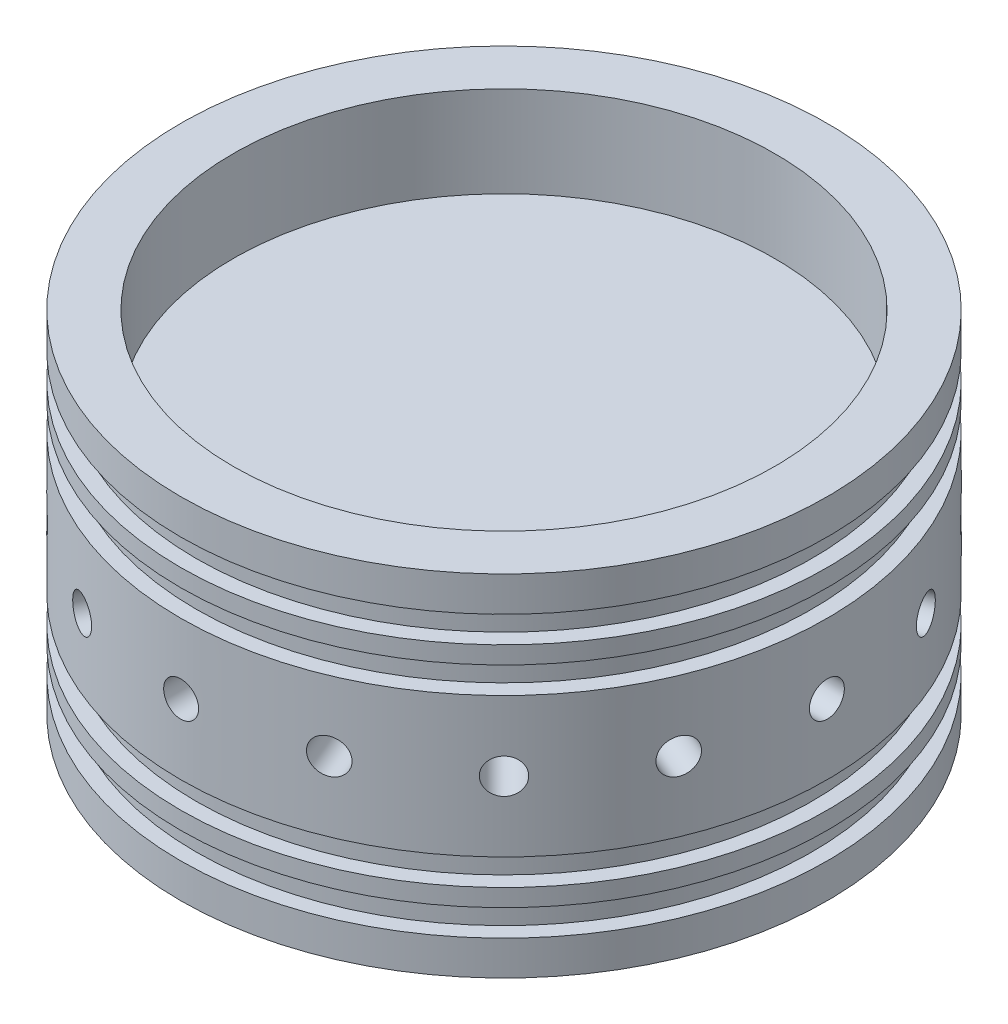
SolidWorks part; units mm, degrees
material "6061-T6 (SS)"
ref_plane "Front Plane" through (0, 0, 0) normal (0, 0, 1) x (1, 0, 0)
ref_plane "Top Plane" through (0, 0, 0) normal (0, 1, 0) x (1, 0, 0)
ref_plane "Right Plane" through (0, 0, 0) normal (1, 0, 0) x (0, 0, -1)
sketch "Sketch1" plane through (0, 0, 0) normal (0, 0, 1) x (1, 0, 0)
  line L11 (0, 0) -> (-58.7375, 0)
  line L13 (-58.7375, 31.8262) -> (-49.2125, 31.8262)
  line L14 (0, 0) -> (0, 15.3162)
  line L15 (0, 15.3162) -> (-49.2125, 15.3162)
  line L16 (-49.2125, 15.3162) -> (-49.2125, 31.8262)
  line L17 (0, 0) -> (0, -15.24)
  line L19 (-58.7375, -31.75) -> (-49.2125, -31.75)
  line L20 (-49.2125, -31.75) -> (-49.2125, -15.24)
  line L21 (-49.2125, -15.24) -> (0, -15.24)
  line L22 (0, 31.75) -> (0, -31.75) construction
  line L23 (-58.7375, 0) -> (-58.7375, 12.7)
  line L24 (-58.7375, 12.7) -> (-55.9181, 12.7)
  line L25 (-55.9181, 12.7) -> (-55.9181, 17.5006)
  line L26 (-55.9181, 17.5006) -> (-58.7375, 17.5006)
  line L27 (-58.7375, 17.5006) -> (-58.7375, 20.6756)
  line L28 (-58.7375, 20.6756) -> (-55.9181, 20.6756)
  line L29 (-55.9181, 20.6756) -> (-55.9181, 25.4762)
  line L30 (-55.9181, 25.4762) -> (-58.7375, 25.4762)
  line L31 (-58.7375, 25.4762) -> (-58.7375, 31.8262)
  line L32 (-58.7375, 0) -> (-58.7375, -12.7)
  line L33 (-58.7375, -12.7) -> (-55.9435, -12.7)
  line L34 (-55.9435, -12.7) -> (-55.9435, -17.5006)
  line L35 (-55.9435, -17.5006) -> (-58.7375, -17.5006)
  line L36 (-58.7375, -17.5006) -> (-58.7375, -20.6756)
  line L37 (-58.7375, -20.6756) -> (-55.9435, -20.6756)
  line L38 (-55.9435, -20.6756) -> (-55.9435, -25.4762)
  line L39 (-55.9435, -25.4762) -> (-58.7375, -25.4762)
  line L40 (-58.7375, -25.4762) -> (-58.7375, -31.75)
  dimension "D1" = 58.7375
  dimension "D2" = 12.7
  dimension "D3" = 4.8006
  dimension "D4" = 4.8006
  dimension "D5" = 3.175
  dimension "D6" = 2.8194
  dimension "D7" = 2.8194
  dimension "D8" = 9.525
  dimension "D9" = 12.7
  dimension "D10" = 4.8006
  dimension "D11" = 4.8006
  dimension "D12" = 3.175
  dimension "D13" = 2.794
  dimension "D14" = 2.794
  dimension "D16" = 9.525
revolve "Revolve1" add sketch "Sketch1" angle 360 about L22 region at (-32.4101, -9.7542, 0) region at (-32.3913, 9.7876, 0)
ref_plane "HoleFacePlane" through (0, 0, 58.7375) normal (0, 0, 1) x (1, 0, 0)
sketch "HoleReference" plane through (0, 0, 58.7375) normal (0, 0, 1) x (1, 0, 0)
  point P0 (0, 0)
hole_wizard "1/4 (0.25) Diameter Hole1" positions "Sketch3" profile "Sketch4" hole size "1/4" standard "ANSI Inch"
sketch "Sketch3" plane through (0, 0, 58.7375) normal (0, 0, 1) x (1, 0, 0)
  point P0 (0, 0)
sketch "Sketch4" plane through (0, 0, 58.7375) normal (1, 0, 0) x (0, -1, 0)
  line L0 (0, 0) -> (0, 27.3077)
  line L1 (0, 27.3077) -> (3.175, 25.4)
  line L2 (3.175, 25.4) -> (3.175, 0)
  line L5 (3.175, 0) -> (0, 0)
  line L10 (0, 27.3077) -> (-3.175, 25.4) construction
  line L11 (0, -6.35) -> (0, 107.95) construction
  dimension "Hole Dia." = 6.35
  dimension "Hole Depth" = 25.4
  dimension "Drill Angle" = 118
ref_axis "Centerline" through (0, -12.7, 0) along (0, 1, 0)
pattern_circular "HolePattern" count 16 over 360 about axis through (0, -12.7, 0) along (0, 1, 0) of "1/4 (0.25) Diameter Hole1"
